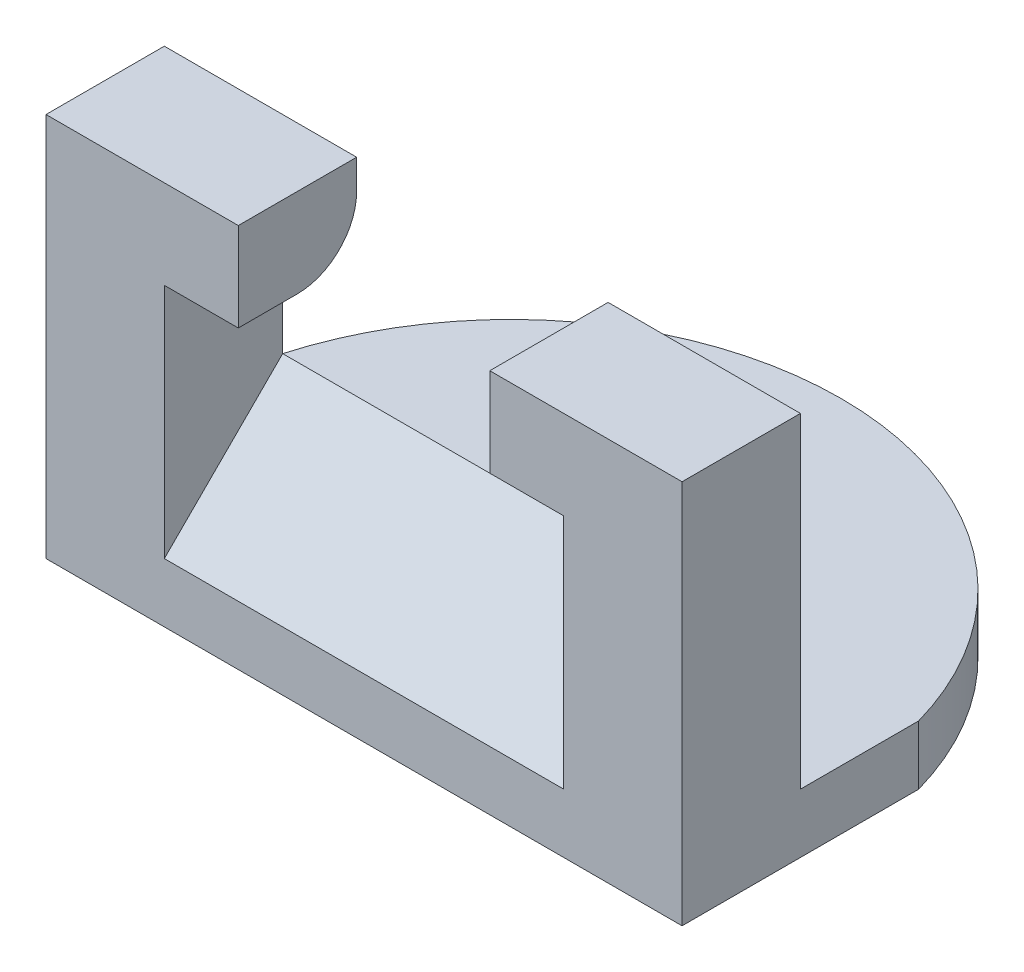
SolidWorks part; units mm, degrees
ref_plane "Front Plane" through (0, 0, 0) normal (0, 0, 1) x (1, 0, 0)
ref_plane "Top Plane" through (0, 0, 0) normal (0, 1, 0) x (1, 0, 0)
ref_plane "Right Plane" through (0, 0, 0) normal (1, 0, 0) x (0, 0, -1)
sketch "Sketch1" plane through (0, 0, 0) normal (0, 1, 0) x (1, 0, 0)
  line L17 (13.9515, -15.679) -> (13.9515, -19.679)
  line L21 (3.2015, -15.679) -> (3.2015, -19.679)
  line L23 (3.2015, -19.679) -> (13.9515, -19.679)
  circle A0 centre (8.5765, -15.929) radius 1.25
  arc A1 (3.2015, -15.679) -> (13.9515, -15.679) centre (8.5765, -17.2036) cw
  dimension "D6" = 2.5
  dimension "D4" = 4
  dimension "D3" = 5.375
  dimension "D1" = 5.375
extrude "ProfileBoss-Extrude1" add sketch "Sketch1" along normal blind 1
sketch "AngleSketch7" plane through (0, 1, 0) normal (0, 1, 0) x (1, 0, 0)
  line L9 (13.9515, -19.679) -> (13.9515, -17.679)
  line L12 (5.2015, -4.929) -> (3.2015, -4.929) construction
  line L24 (3.2015, -19.679) -> (3.2015, -17.679)
  line L25 (3.2015, -17.679) -> (13.9515, -17.679)
  line L28 (3.2015, -19.679) -> (13.9515, -19.679)
  line L29 (3.2015, -15.679) -> (3.2015, -19.679) construction
  line L33 (3.2015, -19.679) -> (13.9515, -19.679) construction
  dimension "D2" = 2
extrude "AngleBoss-Extrude3" add sketch "AngleSketch7" along normal blind 5.5
sketch "UnderRollerSketch10" plane through (0, 0, 19.679) normal (0, 0, 1) x (1, 0, 0)
  line L0 (13.9515, 6.5) -> (13.9515, 0) construction
  line L1 (5.2015, 5) -> (11.9515, 5)
  line L2 (5.2015, 5) -> (5.2015, 3)
  line L3 (5.2015, 3) -> (11.9515, 3)
  line L4 (11.9515, 5) -> (11.9515, 3)
  line L5 (3.2015, 0) -> (13.9515, 0) construction
  line L6 (3.2015, 6.5) -> (3.2015, 0) construction
  line L7 (13.9515, 6.5) -> (13.9515, 0) construction
  dimension "D1" = 2
  dimension "D2" = 2
  dimension "D3" = 2
extrude "UnderRollerCut-Extrude5" cut sketch "UnderRollerSketch10" against normal through all
fillet "OutFillet22" radius 1 1 edges at (8.5765, 5, 17.679)
sketch "Sketch2" plane through (0, 6.5, 0) normal (0, 1, 0) x (1, 0, 0)
  line L0 (13.9515, -17.679) -> (3.2015, -17.679) construction
  line L1 (6.4515, -17.679) -> (10.7015, -17.679)
  line L2 (6.4515, -17.679) -> (6.4515, -19.679)
  line L3 (6.4515, -19.679) -> (10.7015, -19.679)
  line L4 (10.7015, -17.679) -> (10.7015, -19.679)
  line L5 (3.2015, -19.679) -> (13.9515, -19.679) construction
  line L6 (3.2015, -17.679) -> (3.2015, -19.679) construction
  dimension "D1" = 3.25
  dimension "D2" = 4.25
extrude "OpenningCut-Extrude1" cut sketch "Sketch2" against normal up to next
chamfer "OutChamfer1" distance 2 angle 45 1 edges at (8.5765, 3, 19.679)
equation "\"RibbonCableWidth\"= 6.75mm"
equation "\"RibbonCableHypotonus\"= sqr ( \"RibbonCableWidth\" ^ 2 * 2 )"
equation "\"M2.5HoleDiameter\"= 2.5mm"
equation "\"FastenerTabHoleCenterFromSide\"= 2mm"
equation "\"ClampBridgeWidth\"= 2mm"
equation "\"ClampWidth\"= \"RibbonCableWidth\" + \"ClampBridgeWidth\" * 2"
equation "\"ClampBridgeHeight\"= 6.5mm"
equation "\"BaseBoss\"= 1mm"
equation "\"D1@ProfileBoss-Extrude1\" = 1mm"
equation "\"D1@AngleBoss-Extrude3\" = \"ClampBridgeHeight\" - \"BaseBoss\""
equation "\"D1@UnderRollerSketch10\" = \"ClampBridgeWidth\""
equation "\"D1@UnderRollerCut-Extrude5\" = \"ClampBridgeWidth\""
equation "\"D6@Sketch1\"=\"M2.5HoleDiameter\""
equation "\"D4@Sketch1\"=\"ClampBridgeWidth\"*2"
equation "\"RibbonCableLowerWallHeight\"= 2mm"
equation "\"D2@AngleSketch7\"=\"ClampBridgeWidth\""
equation "\"D1@OutChamfer1\"=\"RibbonCableLowerWallHeight\""
equation "\"D3@UnderRollerSketch10\"=\"ClampBridgeWidth\""
equation "\"D2@Sketch2\"=\"RibbonCableWidth\" - 2.5"
equation "\"D1@Sketch2\"=(\"ClampWidth\" - \"RibbonCableWidth\" +2.5)/2"
